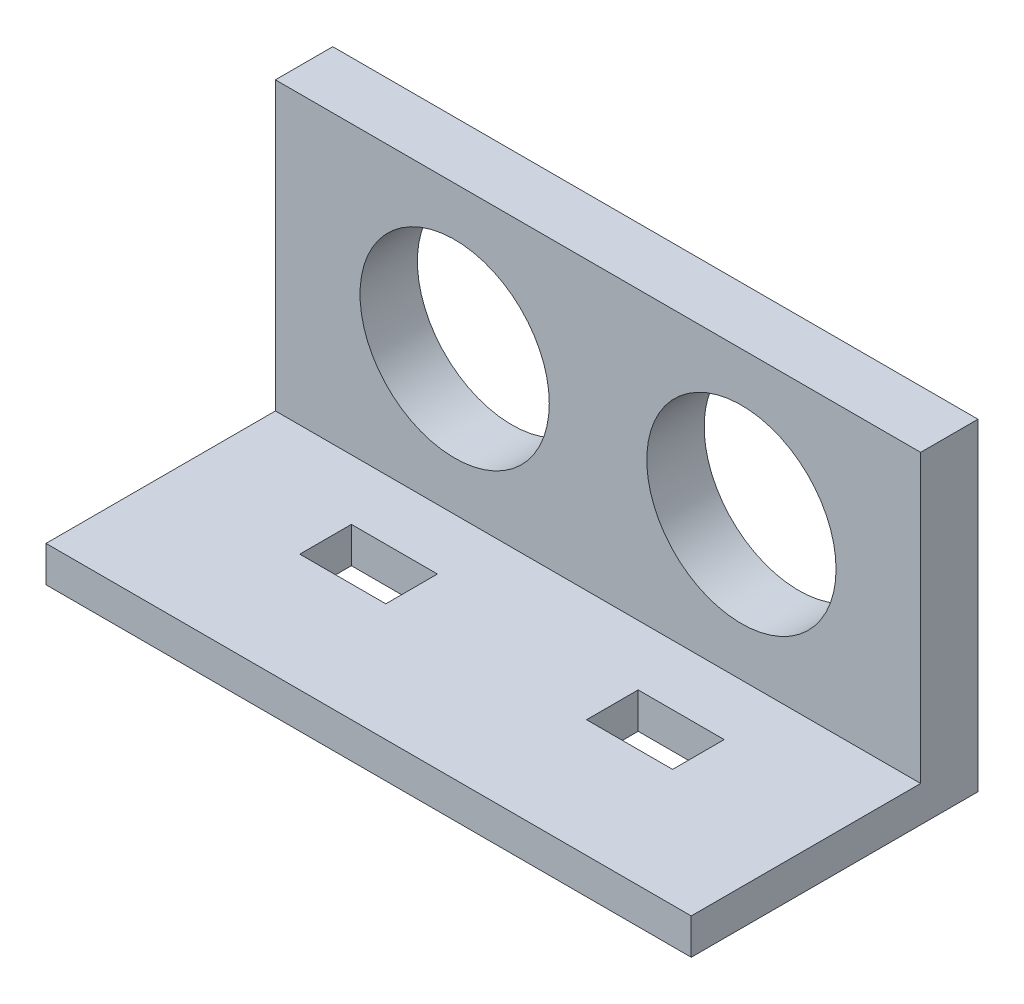
SolidWorks part; units mm, degrees
ref_plane "Front Plane" through (0, 0, 0) normal (0, 0, 1) x (1, 0, 0)
ref_plane "Top Plane" through (0, 0, 0) normal (0, 1, 0) x (1, 0, 0)
ref_plane "Right Plane" through (0, 0, 0) normal (1, 0, 0) x (0, 0, -1)
sketch "Sketch1" plane through (0, 0, 0) normal (0, 0, 1) x (1, 0, 0)
  line L1 (-28.575, 12.7) -> (28.575, 12.7)
  line L2 (-28.575, 12.7) -> (-28.575, -12.7)
  line L3 (-28.575, -12.7) -> (28.575, -12.7)
  line L4 (28.575, 12.7) -> (28.575, -12.7)
  line L5 (-28.575, 12.7) -> (28.575, -12.7) construction
  line L6 (-28.575, -12.7) -> (28.575, 12.7) construction
  circle A0 centre (-12.7, 0) radius 8.382
  circle A1 centre (12.7, 0) radius 8.382
  point P0 (0, 0)
  point P1 (0, 0)
  dimension "D2" = 16.764
  dimension "D1" = 25.4
  dimension "D3" = 12.7
  dimension "D4" = 25.4
  dimension "D5" = 57.15
extrude "Boss-Extrude1" add sketch "Sketch1" against normal blind 5.08
sketch "Sketch3" plane through (-28.575, 0, 0) normal (-1, 0, 0) x (0, 0, 1)
  line L1 (-5.08, -12.7) -> (20.32, -12.7)
  line L2 (-5.08, -12.7) -> (-5.08, -15.875)
  line L3 (-5.08, -15.875) -> (20.32, -15.875)
  line L4 (20.32, -12.7) -> (20.32, -15.875)
  dimension "D1" = 25.4
  dimension "D2" = 3.175
extrude "Boss-Extrude2" add sketch "Sketch3" against normal up to surface (57.15 mm away) up to face at (28.575, 0, -2.54)
sketch "Sketch4" plane through (0, -12.7, 0) normal (0, 1, 0) x (1, 0, 0)
  line L1 (-16.51, -5.334) -> (-8.89, -5.334)
  line L2 (-16.51, -5.334) -> (-16.51, -9.906)
  line L3 (-16.51, -9.906) -> (-8.89, -9.906)
  line L4 (-8.89, -5.334) -> (-8.89, -9.906)
  line L5 (8.89, -5.334) -> (16.51, -5.334)
  line L6 (8.89, -5.334) -> (8.89, -9.906)
  line L7 (8.89, -9.906) -> (16.51, -9.906)
  line L8 (16.51, -5.334) -> (16.51, -9.906)
  line L10 (28.575, -20.32) -> (-28.575, -20.32) construction
  point P8 (-8.89, -7.62)
  point P9 (8.89, -7.62)
  point P14 (-12.7, -5.334)
  point P15 (12.7, -5.334)
  dimension "D1" = 4.572
  dimension "D2" = 4.572
  dimension "D3" = 12.7
  dimension "D4" = 12.7
  dimension "D5" = 7.62
  dimension "D6" = 7.62
  dimension "D7" = 8.382
  dimension "D8" = 8.382
extrude "Cut-Extrude1" cut sketch "Sketch4" against normal blind 5.08
sketch "Sketch5" plane through (0, -15.875, 0) normal (0, -1, 0) x (1, 0, 0)
  line L0 (16.51, 5.334) -> (16.51, 9.906) construction
  line L1 (-26.035, 5.08) -> (-20.955, 5.08)
  line L2 (-26.035, 5.08) -> (-26.035, 10.16)
  line L3 (-26.035, 10.16) -> (-20.955, 10.16)
  line L4 (-20.955, 5.08) -> (-20.955, 10.16)
  line L5 (-26.035, 5.08) -> (-20.955, 10.16) construction
  line L6 (-26.035, 10.16) -> (-20.955, 5.08) construction
  line L7 (20.955, 5.08) -> (26.035, 5.08)
  line L8 (20.955, 5.08) -> (20.955, 10.16)
  line L9 (20.955, 10.16) -> (26.035, 10.16)
  line L10 (26.035, 5.08) -> (26.035, 10.16)
  line L11 (20.955, 5.08) -> (26.035, 10.16) construction
  line L12 (20.955, 10.16) -> (26.035, 5.08) construction
  line L13 (-16.51, 9.906) -> (-16.51, 5.334) construction
  line L14 (-28.575, -5.08) -> (-28.575, 20.32) construction
  line L15 (28.575, -5.08) -> (28.575, 20.32) construction
  point P0 (-23.495, 7.62)
  point P5 (23.495, 7.62)
  point P10 (16.51, 7.62)
  point P13 (-16.51, 7.62)
  dimension "D1" = 5.08
  dimension "D2" = 5.08
  dimension "D3" = 5.08
  dimension "D4" = 5.08
  dimension "D5" = 0
  dimension "D6" = 0
  dimension "D7" = 5.08
  dimension "D8" = 5.08
extrude "Boss-Extrude3" add sketch "Sketch5" along normal blind 2.54
chamfer "Chamfer1" distance 2.54 angle 45 2 edges at (26.035, -18.415, 7.62) (-26.035, -18.415, 7.62)
